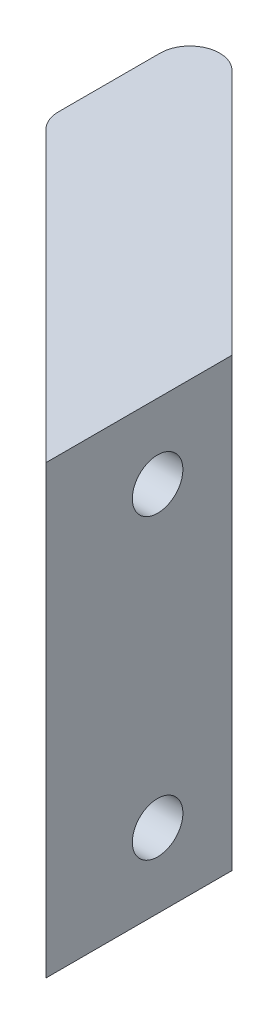
SolidWorks part; units mm, degrees
ref_plane "Front Plane" through (0, 0, 0) normal (0, 0, 1) x (1, 0, 0)
ref_plane "Top Plane" through (0, 0, 0) normal (0, 1, 0) x (1, 0, 0)
ref_plane "Right Plane" through (0, 0, 0) normal (1, 0, 0) x (0, 0, -1)
ref_axis "X" through (-88.99, 0, 0) along (1, 0, 0)
ref_axis "Y" through (0, 55, 0) along (0, -1, 0)
ref_axis "Z" through (0, 0, -88.99) along (0, 0, 1)
sketch "Sketch1" plane through (0, 0, 0) normal (0, 1, 0) x (1, 0, 0)
  line L10 (0, 0) -> (0, -7.5)
  line L11 (0, -7.5) -> (-20, 12.5)
  line L12 (-20, 12.5) -> (-20, 25)
  line L13 (-20, 25) -> (0, 5)
  line L14 (0, 5) -> (0, 0)
  dimension "D1" = 7.5
  dimension "D2" = 45
  dimension "D3" = 5
  dimension "D4" = 20
extrude "Boss-Extrude1" add sketch "Sketch1" along normal mid plane 30
sketch "Sketch2" plane through (0, 0, 0) normal (1, 0, 0) x (0, 0, -1)
  line L0 (0, 10) -> (0, -10) construction
  circle A0 centre (0, 10) radius 3
  circle A1 centre (0, -10) radius 3
  point P4 (0, 0)
  dimension "D2" = 6
  dimension "D1" = 20
extrude "Cut-Extrude1" cut sketch "Sketch2" against normal through all from offset 4 offset against normal yes
sketch "Sketch5" plane through (-4, 0, 0) normal (-1, 0, 0) x (0, 0, 1)
  point P0 (0, 10)
  point P3 (0, -10)
hole_wizard "M3 Clearance Hole1" positions "Sketch5" profile "Sketch6" hole size "M3" standard "ANSI Metric" end condition through all
sketch "Sketch6" plane through (-4, 10, 0) normal (0, 1, 0) x (0, 0, 1)
  line L0 (0, 0) -> (0, 4)
  line L1 (0, 4) -> (1.7, 4)
  line L2 (1.7, 4) -> (1.7, 0)
  line L5 (1.7, 0) -> (0, 0)
  line L11 (0, -6.35) -> (0, 107.95) construction
  dimension "Thru Hole Dia." = 3.4
  dimension "Thru Hole Depth" = 4
fillet "Fillet2" radius 2 2 edges at (-20, 0, -12.5) (-20, 0, -25)
